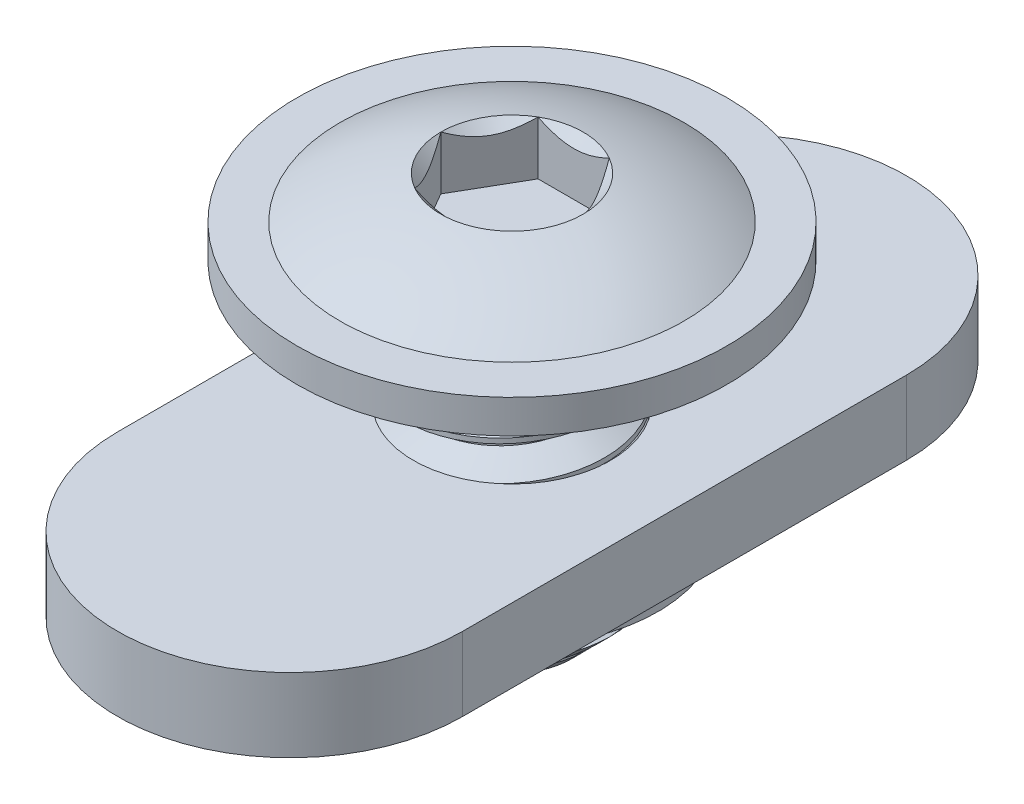
SolidWorks part; units mm, degrees
ref_plane "Front Plane" through (0, 0, 0) normal (0, 0, 1) x (1, 0, 0)
ref_plane "Top Plane" through (0, 0, 0) normal (0, 1, 0) x (1, 0, 0)
ref_plane "Right Plane" through (0, 0, 0) normal (1, 0, 0) x (0, 0, -1)
sketch "Sketch1" plane through (0, 0, 0) normal (0, 0, 1) x (1, 0, 0)
  line L0 (0, 0) -> (0, 53.1234) construction
  line L1 (0, -5.08) -> (-3.175, -5.08)
  line L2 (-3.175, -5.08) -> (-3.175, 5.08)
  line L3 (-3.175, 5.08) -> (-6.9215, 5.08)
  line L4 (-6.9215, 5.08) -> (-6.9215, 6.157)
  line L5 (-6.9215, 6.157) -> (-5.5372, 6.157)
  line L6 (0, -5.08) -> (0, 7.7724)
  arc A0 (-5.5372, 6.157) -> (0, 7.7724) centre (0, -2.5252) cw
  dimension "screw od" = 6.35
  dimension "head od" = 13.843
  dimension "D3" = 11.0744
  dimension "D4" = 1.077
  dimension "head height" = 2.6924
  dimension "screw length" = 10.16
sketch "Sketch2" plane through (0, 0, 0) normal (0, 0, 1) x (1, 0, 0)
  line L0 (0, -5.08) -> (0, 7.7724) construction
  line L1 (-3.175, 5.08) -> (-6.9215, 5.08) construction
  line L2 (0, -5.08) -> (-3.175, -5.08) construction
  line L3 (-3.175, -5.08) -> (-3.175, 5.08) construction
  line L4 (0, -5.08) -> (0, 5.08)
  line L5 (0, 5.08) -> (-3.175, 5.08)
  line L6 (0, -5.08) -> (-3.175, -5.08)
  line L7 (-3.175, -5.08) -> (-3.175, 5.08)
  dimension "D1" = 10.16
revolve "Revolve2" add sketch "Sketch2" angle 360 about L0
sketch "Sketch3" plane through (0, 5.08, 0) normal (0, 1, 0) x (1, 0, 0)
  circle A1 centre (0, 0) radius 3.175
  circle A2 centre (0, 0) radius 3.175
  dimension "D1" = 0
curve "Helix/Spiral1" pitch 1.27 height 14.9225 turns 11.75 parameters "pitch"=1.27
chamfer "Chamfer1" distance 1.27 angle 45 1 edges at (0, -5.08, -3.175)
sketch "Sketch4" plane through (0, 0, 0) normal (0, 0, 1) x (1, 0, 0)
  line L0 (3.175, 6.1912) -> (3.175, 5.08)
  line L1 (3.175, 5.08) -> (2.3501, 5.5562)
  line L2 (2.3501, 5.5562) -> (2.3501, 5.715)
  line L3 (2.3501, 5.715) -> (3.175, 6.1912)
  line L4 (2.3501, 5.6356) -> (3.175, 5.6356) construction
  line L5 (2.7626, 5.3181) -> (2.7626, 5.9531) construction
  line L7 (3.175, 5.08) -> (-3.175, 5.08) construction
  dimension "D1" = 60
  dimension "D2" = 0.1588
  dimension "D3" = 0.635
sweep "Cut-Sweep1" cut profiles "Sketch4" path "Helix/Spiral1"
sketch "Sketch5" plane through (0, 0, 0) normal (0, 0, 1) x (1, 0, 0)
  line L0 (0, -5.08) -> (0, 7.7724) construction
  line L1 (-3.175, 5.08) -> (-6.9215, 5.08) construction
  line L2 (-6.9215, 6.157) -> (-5.5372, 6.157) construction
  line L3 (-6.9215, 5.08) -> (-6.9215, 6.157) construction
  line L4 (0, 5.08) -> (0, 7.7724)
  line L5 (0, 5.08) -> (-6.9215, 5.08)
  line L6 (-6.9215, 6.157) -> (-5.5372, 6.157)
  line L7 (-6.9215, 5.08) -> (-6.9215, 6.157)
  arc A0 (0, 7.7724) -> (-5.5372, 6.157) centre (0, -2.5252) ccw construction
  arc A1 (0, 7.7724) -> (-5.5372, 6.157) centre (0, -2.5252) ccw
revolve "Revolve3" add sketch "Sketch5" angle 360 about L0
ref_plane "Plane1" through (0, 7.7724, 0) normal (0, 1, 0) x (-1, 0, 0)
sketch "Sketch6" plane through (0, 7.7724, 0) normal (0, 1, 0) x (-1, 0, 0)
  line L1 (1.1457, 1.9844) -> (-1.1457, 1.9844)
  line L2 (-1.1457, 1.9844) -> (-2.2914, 0)
  line L3 (-2.2914, 0) -> (-1.1457, -1.9844)
  line L4 (-1.1457, -1.9844) -> (1.1457, -1.9844)
  line L5 (1.1457, -1.9844) -> (2.2914, 0)
  line L6 (2.2914, 0) -> (1.1457, 1.9844)
  circle A0 centre (0, 0) radius 1.9844 construction
  dimension "hex" = 3.9688
extrude "Cut-Extrude1" cut sketch "Sketch6" against normal blind 1.9844
ref_plane "Plane2" through (0, 7.5142, 0) normal (0, 1, 0) x (-1, 0, 0)
sketch "Sketch7" plane through (0, 7.5142, 0) normal (0, 1, 0) x (-1, 0, 0)
  circle A0 centre (0, 0) radius 2.2914
extrude "Cut-Extrude2" cut sketch "Sketch7" against normal up to surface (1.7262 mm away) draft 45 and the other way through all
ref_plane "Plane3" through (0, -0.635, 0) normal (0, -1, 0) x (1, 0, 0)
sketch "Sketch8" plane through (0, -0.635, 0) normal (0, -1, 0) x (1, 0, 0)
  line L0 (0, -7.1437) -> (0, 7.1437) construction
  line L2 (-5.5563, 7.1437) -> (-5.5563, -7.1437)
  line L4 (5.5563, 7.1437) -> (5.5563, -7.1437)
  circle A0 centre (0, 0) radius 3.175
  arc A1 (-5.5563, 7.1437) -> (5.5563, 7.1437) centre (0, 7.1437) cw
  arc A2 (-5.5563, -7.1437) -> (5.5563, -7.1437) centre (0, -7.1437) ccw
  dimension "D1" = 6.35
  dimension "D3" = 25.4
  dimension "D2" = 11.1125
extrude "Extrude1" add sketch "Sketch8" along normal mid plane 3.4544 separate body
sketch "Sketch9" plane through (0, -2.3622, 0) normal (0, -1, 0) x (1, 0, 0)
  line L2 (5.5563, -7.1437) -> (5.5563, 7.1437)
  line L3 (-5.5563, 7.1437) -> (-5.5563, -7.1437)
  line L4 (5.5563, -7.1437) -> (5.5563, 7.1437)
  line L5 (-5.5563, 7.1437) -> (-5.5563, -7.1437)
  arc A2 (-5.5563, -7.1437) -> (5.5563, -7.1437) centre (0, -7.1437) ccw
  arc A3 (5.5563, 7.1437) -> (-5.5563, 7.1437) centre (0, 7.1437) ccw
  arc A4 (-5.5563, -7.1437) -> (5.5563, -7.1437) centre (0, -7.1437) ccw
  arc A5 (5.5563, 7.1437) -> (-5.5563, 7.1437) centre (0, 7.1437) ccw
  circle A6 centre (0, 0) radius 4.699
  circle A7 centre (0, 0) radius 4.699
  dimension "D1" = 0
  dimension "D2" = 1.524
extrude "Cut-Extrude3" cut sketch "Sketch9" against normal offset from surface (1.0795 mm away) 2.3749 up to face at (0, 1.0922, 0)
sketch "Sketch10" [suppressed] plane through (0, 7.9375, 0) normal (0, -1, 0) x (1, 0, 0)
  line L0 (-8.255, -12.3888) -> (-8.255, 2.8511)
  line L1 (8.255, 2.8511) -> (8.255, -12.3888)
  line L2 (-14.9844, 7.9311) -> (0, 7.9311) construction
  circle A0 centre (0, 0) radius 3.9688
  arc A1 (8.255, 2.8511) -> (-8.255, 2.8511) centre (0, -1.316) ccw
  arc A2 (-8.255, -12.3888) -> (8.255, -12.3888) centre (0, -8.2217) ccw
  dimension "D2" = 3.9624
  dimension "D3" = 16.51
  dimension "D4" = 5.08
  dimension "D5" = 6.35
  dimension "D1" = 25.4
extrude "Extrude2" [suppressed] add sketch "Sketch10" along normal mid plane 5.3594 separate body
sketch "Sketch11" [suppressed] plane through (0, 5.2578, 0) normal (0, -1, 0) x (1, 0, 0)
  line L2 (8.255, -12.3888) -> (8.255, 2.8511)
  line L3 (-8.255, 2.8512) -> (-8.255, -12.3888)
  line L4 (8.255, -12.3888) -> (8.255, 2.8511)
  line L5 (-8.255, 2.8512) -> (-8.255, -12.3888)
  circle A2 centre (0, 0) radius 5.4927
  circle A3 centre (0, 0) radius 5.4927
  arc A5 (-8.255, -12.3888) -> (8.255, -12.3888) centre (0, -8.2217) ccw
  arc A6 (8.255, 2.8511) -> (-8.255, 2.8512) centre (0, -1.316) ccw
  arc A7 (-8.255, -12.3888) -> (8.255, -12.3888) centre (0, -8.2217) ccw
  arc A8 (8.255, 2.8511) -> (-8.255, 2.8512) centre (0, -1.316) ccw
  dimension "D1" = 1.524
  dimension "D2" = 0
extrude "Cut-Extrude4" [suppressed] cut sketch "Sketch11" against normal offset from surface (1.651 mm away) 3.7084
sketch "Sketch12" [suppressed] plane through (0, 0, 0) normal (0, 0, 1) x (1, 0, 0)
  line L0 (-6.7564, 17.78) -> (-5.4051, 17.78) construction
  line L1 (-6.7564, 17.78) -> (-5.4051, 17.78)
  line L2 (10.3378, 20.0315) -> (-10.3378, 20.0315) construction
  line L3 (0, 0) -> (0, 53.1234) construction
  line L4 (-3.9688, 15.875) -> (-6.7564, 15.875) construction
  line L5 (-9.398, 15.875) -> (-3.9688, 15.875)
  line L6 (-9.398, 15.875) -> (-9.398, 14.605)
  line L7 (-9.398, 14.605) -> (-3.9688, 14.605)
  line L8 (-3.9688, 15.875) -> (-3.9688, 14.605)
  arc A0 (0, 20.6375) -> (-5.4051, 17.78) centre (0, 14.0967) ccw construction
  arc A1 (-2.7496, 20.0315) -> (-5.4051, 17.78) centre (0, 14.0967) ccw
  arc A2 (-6.7564, 17.78) -> (-2.7496, 20.0315) centre (0, 10.4472) cw
  dimension "D1" = 9.398
  dimension "D2" = 1.27
revolve "Revolve4" [suppressed] add sketch "Sketch12" angle 360 about L0
sketch "Sketch13" [suppressed] plane through (0, 6.35, 0) normal (0, -1, 0) x (1, 0, 0)
  line L0 (-7.9375, 4.7562) -> (-7.9375, -17.4688)
  line L1 (7.9375, 4.7562) -> (7.9375, -17.4688)
  circle A0 centre (0, 0) radius 3.9688
  arc A1 (-7.9375, 4.7562) -> (7.9375, 4.7562) centre (0, -3.5782) cw
  arc A2 (-7.9375, -17.4688) -> (7.9375, -17.4688) centre (0, -9.1345) ccw
  dimension "D2" = 28.575
  dimension "D3" = 3.9624
  dimension "D4" = 7.9375
  dimension "D1" = 15.875
  dimension "D5" = 3.175
extrude "Extrude4" [suppressed] add sketch "Sketch13" along normal mid plane 5.8928 separate body
sketch "Sketch14" [suppressed] plane through (0, 3.4036, 0) normal (0, -1, 0) x (1, 0, 0)
  line L2 (-7.9375, 4.7561) -> (-7.9375, -17.4688)
  line L3 (7.9375, -17.4688) -> (7.9375, 4.7562)
  line L4 (-7.9375, 4.7561) -> (-7.9375, -17.4688)
  line L5 (7.9375, -17.4688) -> (7.9375, 4.7562)
  arc A2 (7.9375, 4.7562) -> (-7.9375, 4.7561) centre (0, -3.5782) ccw
  arc A3 (-7.9375, -17.4688) -> (7.9375, -17.4688) centre (0, -9.1345) ccw
  arc A4 (7.9375, 4.7562) -> (-7.9375, 4.7561) centre (0, -3.5782) ccw
  arc A5 (-7.9375, -17.4688) -> (7.9375, -17.4688) centre (0, -9.1345) ccw
  circle A6 centre (0, 0) radius 5.4927
  circle A7 centre (0, 0) radius 5.4927
  dimension "D1" = 0
  dimension "D2" = 1.524
extrude "Cut-Extrude7" [suppressed] cut sketch "Sketch14" against normal offset from surface (1.8034 mm away) 4.0894
sketch "Sketch15" [suppressed] plane through (0, 0, 0) normal (0, 0, 1) x (1, 0, 0)
  line L0 (-6.6675, 19.6774) -> (-5.334, 19.6774) construction
  line L1 (-6.6675, 19.6774) -> (-5.334, 19.6774)
  line L2 (9.2481, 22.5402) -> (-9.2481, 22.5402) construction
  line L3 (0, 0) -> (0, 53.1234) construction
  arc A0 (0, 22.9997) -> (-5.334, 19.6774) centre (0, 17.0567) ccw construction
  arc A1 (-2.2914, 22.5402) -> (-5.334, 19.6774) centre (0, 17.0567) ccw
  arc A2 (-2.2914, 22.5402) -> (-6.6675, 19.6774) centre (0, 14.2615) ccw
revolve "Revolve5" [suppressed] add sketch "Sketch15" angle 360 about L0
sketch "Sketch16" [suppressed] plane through (0, 3.175, 0) normal (0, -1, 0) x (1, 0, 0)
  line L0 (-6.3881, 8.443) -> (-6.3881, -33.843)
  line L1 (6.3881, 8.443) -> (6.3881, -33.843)
  line L2 (0, -25.4) -> (0, 0) construction
  line L3 (0, -12.7) -> (-6.3881, -12.7) construction
  line L4 (-6.3881, -27.1355) -> (-6.3881, 1.7355) construction
  circle A0 centre (0, 0) radius 3.175
  circle A1 centre (0, -25.4) radius 3.175
  arc A2 (-6.3881, 8.443) -> (6.3881, 8.443) centre (0, 1.7355) cw
  arc A3 (-6.3881, -33.843) -> (6.3881, -33.843) centre (0, -27.1355) ccw
  dimension "D1" = 25.4
  dimension "D2" = 6.35
  dimension "D4" = 47.3964
  dimension "D3" = 12.7762
  dimension "D5" = 2.5552
extrude "Extrude5" [suppressed] add sketch "Sketch16" along normal mid plane 4.0894 separate body
sketch "Sketch17" [suppressed] plane through (0, 1.1303, 0) normal (0, -1, 0) x (1, 0, 0)
  line L2 (-6.3881, 8.443) -> (-6.3881, -33.843)
  line L3 (6.3881, -33.843) -> (6.3881, 8.443)
  line L4 (-6.3881, 8.443) -> (-6.3881, -33.843)
  line L5 (6.3881, -33.843) -> (6.3881, 8.443)
  arc A2 (6.3881, 8.443) -> (-6.3881, 8.443) centre (0, 1.7355) ccw
  arc A3 (-6.3881, -33.843) -> (6.3881, -33.843) centre (0, -27.1355) ccw
  arc A4 (6.3881, 8.443) -> (-6.3881, 8.443) centre (0, 1.7355) ccw
  arc A5 (-6.3881, -33.843) -> (6.3881, -33.843) centre (0, -27.1355) ccw
  circle A6 centre (0, -25.4) radius 4.699
  circle A7 centre (0, -25.4) radius 4.699
  circle A10 centre (0, 0) radius 4.699
  circle A11 centre (0, 0) radius 4.699
  dimension "D1" = 0
  dimension "D2" = 1.524
  dimension "D3" = 1.524
pattern_linear "LPattern1" [suppressed] count 2 spacing 25.4
extrude "Cut-Extrude9" [suppressed] cut sketch "Sketch17" against normal offset from surface (1.4224 mm away) 2.667
sketch "Sketch18" [suppressed] plane through (0, 7.9375, 0) normal (0, -1, 0) x (1, 0, 0)
  line L0 (-7.9375, 13.462) -> (-7.9375, -51.562)
  line L1 (7.9375, 13.462) -> (7.9375, -51.562)
  line L2 (0, 0) -> (0, -38.1) construction
  line L3 (0, -19.05) -> (-7.9375, -19.05) construction
  line L4 (0, -19.05) -> (7.9375, -19.05) construction
  circle A0 centre (0, 0) radius 3.9688
  circle A1 centre (0, -38.1) radius 3.9688
  arc A2 (-7.9375, 13.462) -> (7.9375, 13.462) centre (0, 5.1276) cw
  arc A3 (-7.9375, -51.562) -> (7.9375, -51.562) centre (0, -43.2276) ccw
  dimension "D1" = 38.1
  dimension "D2" = 7.9375
  dimension "D4" = 3.175
  dimension "D5" = 71.374
  dimension "D3" = 15.875
extrude "Extrude6" [suppressed] add sketch "Sketch18" along normal mid plane 5.9944 separate body
sketch "Sketch19" [suppressed] plane through (0, 4.9403, 0) normal (0, -1, 0) x (1, 0, 0)
  line L2 (-7.9375, 13.462) -> (-7.9375, -51.562)
  line L3 (7.9375, -51.562) -> (7.9375, 13.462)
  line L4 (-7.9375, 13.462) -> (-7.9375, -51.562)
  line L5 (7.9375, -51.562) -> (7.9375, 13.462)
  arc A2 (7.9375, 13.462) -> (-7.9375, 13.462) centre (0, 5.1276) ccw
  arc A3 (-7.9375, -51.562) -> (7.9375, -51.562) centre (0, -43.2276) ccw
  arc A4 (7.9375, 13.462) -> (-7.9375, 13.462) centre (0, 5.1276) ccw
  arc A5 (-7.9375, -51.562) -> (7.9375, -51.562) centre (0, -43.2276) ccw
  circle A6 centre (0, 0) radius 5.4927
  circle A7 centre (0, 0) radius 5.4927
  circle A9 centre (0, -38.1) radius 5.4928
  circle A10 centre (0, -38.1) radius 5.4928
  dimension "D1" = 0
  dimension "D2" = 1.524
  dimension "D3" = 1.524
extrude "Cut-Extrude10" [suppressed] cut sketch "Sketch19" against normal offset from surface (2.1844 mm away) 3.81
pattern_linear "LPattern2" [suppressed] count 2 spacing 38.1
equation "\"D2@Sketch4\" = \"pitch@Helix/Spiral1\"*.125"
equation "\"D3@Sketch4\" = \"pitch@Helix/Spiral1\"*.5"
equation "\"D3@Helix/Spiral1\" = \"screw length@Sketch1\"+.18750"
equation "\"D1@Chamfer1\" = \"pitch@Helix/Spiral1\""
equation "\"D1@Cut-Extrude1\" = \"hex@Sketch6\"/2"
equation "\"D1@Sketch8\" = \"screw od@Sketch1\""
equation "\"D4@Sketch1\" = \"head height@Sketch1\"/2.5"
equation "\"D3@Sketch1\" = \"head od@Sketch1\"*.8"
equation "\"D5@Sketch10\" = \"screw od@Sketch1\""
equation "\"D4@Sketch10\" = \"D1@Sketch10\"*.2"
equation "\"D5@Sketch13\" = \"D1@Sketch13\"*.2"
equation "\"D5@Sketch16\" = \"D3@Sketch16\"*.2"
equation "\"D4@Sketch18\" = \"D3@Sketch18\"*.2"
